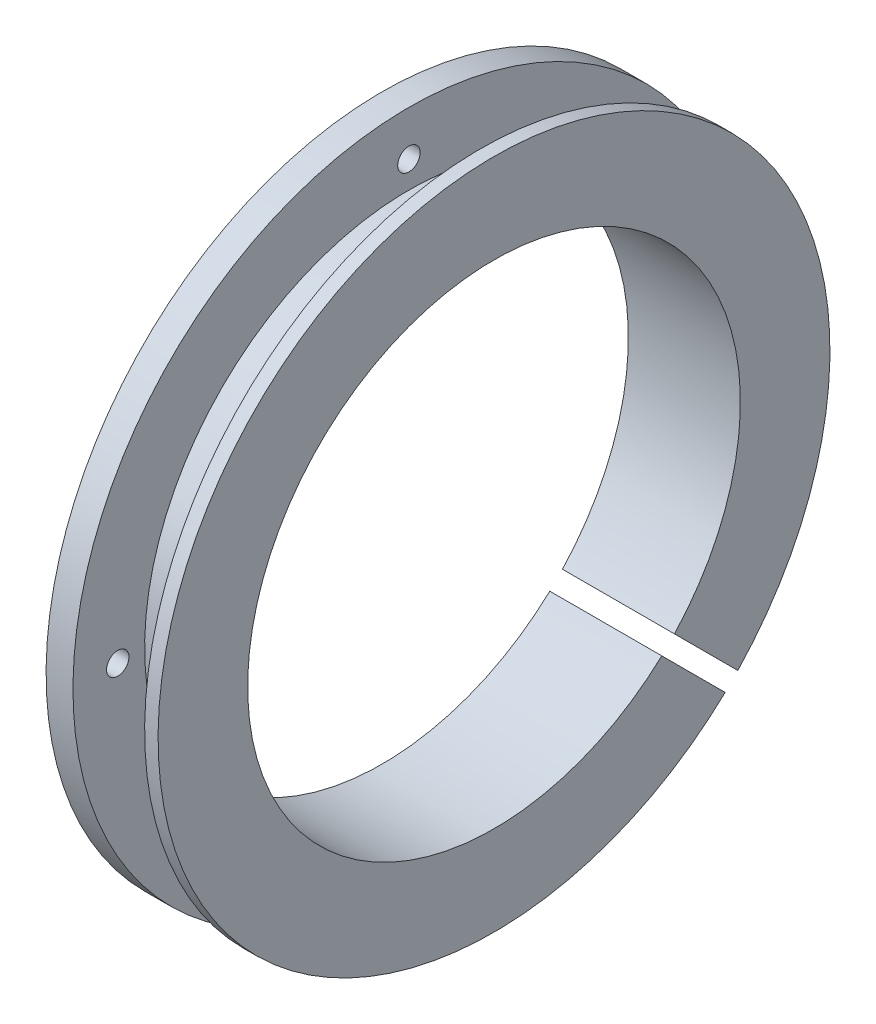
SolidWorks part; units mm, degrees
material "1060 Alloy"
ref_plane "Front Plane" through (0, 0, 0) normal (0, 0, 1) x (1, 0, 0)
ref_plane "Top Plane" through (0, 0, 0) normal (0, 1, 0) x (1, 0, 0)
ref_plane "Right Plane" through (0, 0, 0) normal (1, 0, 0) x (0, 0, -1)
sketch "Sketch1" plane through (0, 0, 0) normal (0, 0, 1) x (1, 0, 0)
  line L0 (0, 0) -> (-116.8977, 0) construction
  line L1 (-12.5, 27.5) -> (0, 27.5)
  line L2 (0, 27.5) -> (0, 37.5)
  line L3 (0, 37.5) -> (-1.5, 37.5)
  line L4 (-1.5, 37.5) -> (-1.5, 29.5)
  line L5 (-1.5, 29.5) -> (-9.5, 29.5)
  line L6 (-9.5, 29.5) -> (-9.5, 37.5)
  line L7 (-9.5, 37.5) -> (-12.5, 37.5)
  line L8 (-12.5, 37.5) -> (-12.5, 27.5)
  dimension "D1" = 37.5
  dimension "D2" = 1.5
  dimension "D3" = 3
  dimension "D4" = 8
  dimension "D5" = 10
  dimension "D6" = 2
revolve "Revolve1" add sketch "Sketch1" angle 360 about L0
hole_wizard "M3x0.5 Tapped Hole1" positions "Sketch5" profile "Sketch4" tap size "M3x0.5" standard "Ansi Metric"
sketch "Sketch5" plane through (-12.5, 0, 0) normal (-1, 0, 0) x (0, 0, 1)
  point P5 (0, -32.5)
  point P8 (-32.5, 0)
  point P14 (32.5, 0)
  point P17 (0, 32.5)
sketch "Sketch4" plane through (-12.5, -32.5, 0) normal (0, 1, 0) x (0, 0, 1)
  line L0 (0, 0) -> (0, 8.2511)
  line L1 (0, 8.2511) -> (1.25, 7.5)
  line L2 (1.25, 7.5) -> (1.25, 0)
  line L5 (1.25, 0) -> (0, 0)
  line L10 (0, 8.2511) -> (-1.25, 7.5) construction
  line L11 (0, -6.35) -> (0, 107.95) construction
  dimension "Tap Drill Dia." = 2.5
  dimension "Tap Drill Depth" = 7.5
  dimension "Drill Angle" = 118
cosmetic thread "Hole Thread5" parameters "D1"=3, "D2"=3
cosmetic thread "Hole Thread6" parameters "D1"=3, "D2"=3
cosmetic thread "Hole Thread7" parameters "D1"=3, "D2"=3
cosmetic thread "Hole Thread8" parameters "D1"=3, "D2"=3
sketch "Sketch6" plane through (0, 0, 0) normal (1, 0, 0) x (0, 0, -1)
  line L0 (0, -37.5) -> (0, 0) construction
  line L1 (0, 0) -> (37.5, 0) construction
  line L2 (37.5, 0) -> (0, -37.5) construction
  line L3 (18.75, -18.75) -> (0, 0) construction
  line L4 (18.75, -18.75) -> (26.5165, -26.5165) construction
  line L5 (27.2236, -25.8094) -> (25.8094, -27.2236)
  line L6 (25.8094, -27.2236) -> (18.7255, -20.1397)
  line L7 (18.7255, -20.1397) -> (20.1397, -18.7255)
  line L8 (20.1397, -18.7255) -> (27.2236, -25.8094)
  circle A0 centre (0, 0) radius 37.5 construction
  circle A1 centre (0, 0) radius 27.5 construction
  dimension "D1" = 1
  dimension "D2" = 1
extrude "Cut-Extrude1" cut sketch "Sketch6" against normal through all
